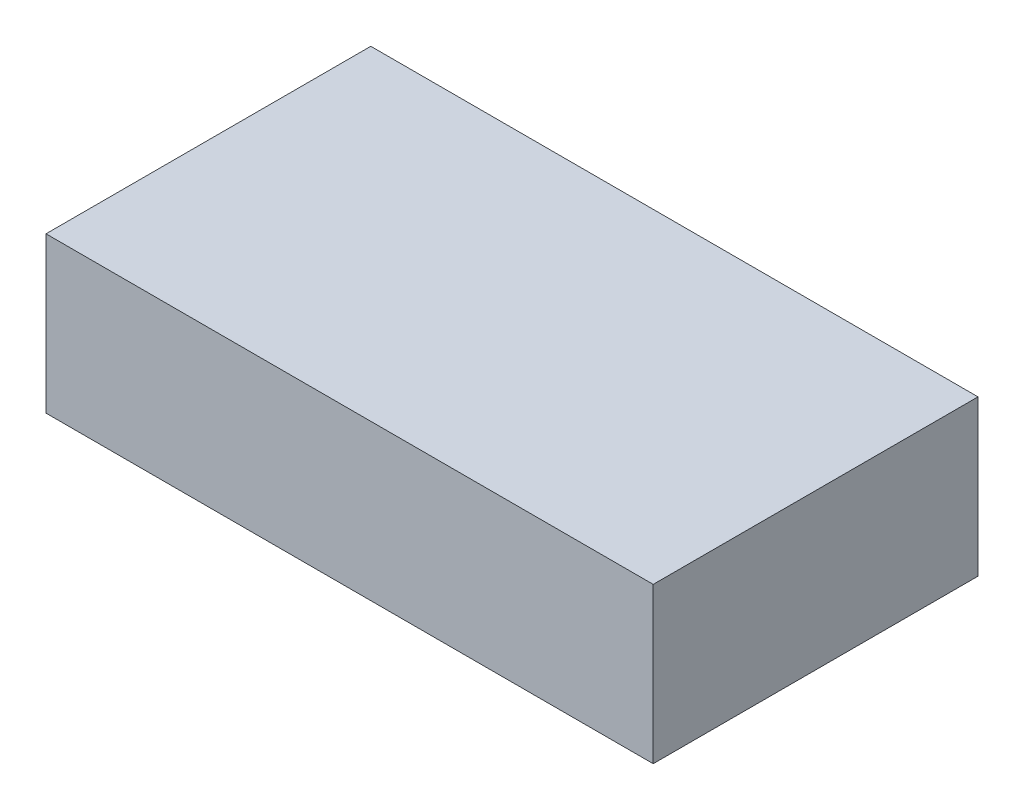
SolidWorks part; units mm, degrees
ref_plane "Front Plane" through (0, 0, 0) normal (0, 0, 1) x (1, 0, 0)
ref_plane "Top Plane" through (0, 0, 0) normal (0, 1, 0) x (1, 0, 0)
ref_plane "Right Plane" through (0, 0, 0) normal (1, 0, 0) x (0, 0, -1)
sketch "Sketch1" plane through (0, 0, 0) normal (0, 1, 0) x (1, 0, 0)
  line L1 (-107.5, -57.5) -> (107.5, -57.5)
  line L2 (-107.5, -57.5) -> (-107.5, 57.5)
  line L3 (-107.5, 57.5) -> (107.5, 57.5)
  line L4 (107.5, -57.5) -> (107.5, 57.5)
  line L5 (-107.5, -57.5) -> (107.5, 57.5) construction
  line L6 (-107.5, 57.5) -> (107.5, -57.5) construction
  point P0 (0, 0)
  dimension "D1" = 115
  dimension "D2" = 215
extrude "Boss-Extrude1" add sketch "Sketch1" along normal blind 55
